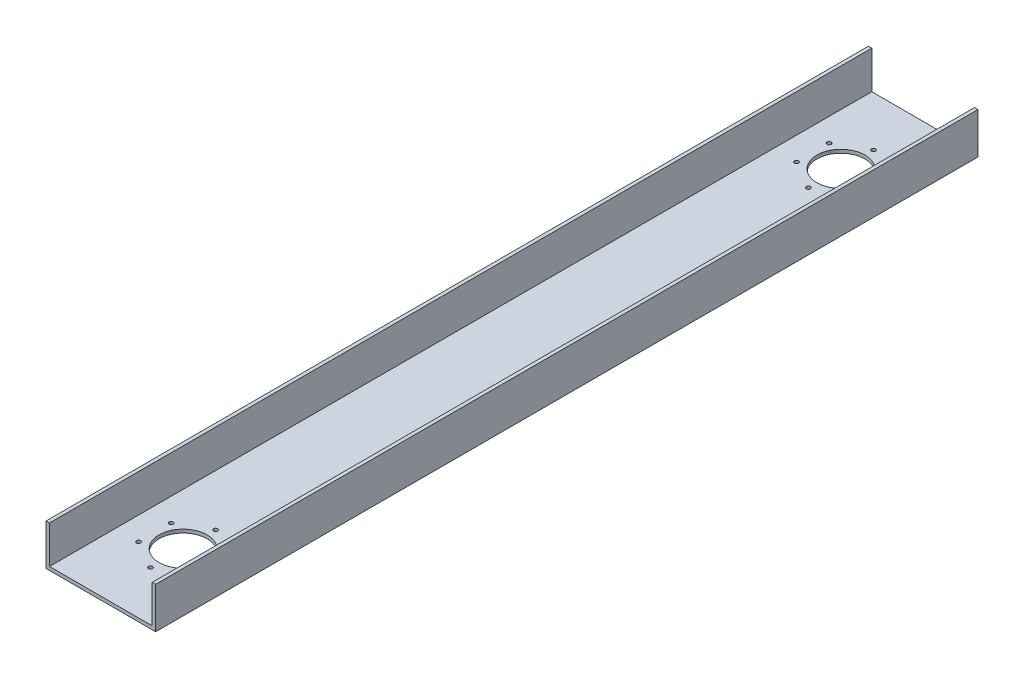
SolidWorks part; units mm, degrees
ref_plane "Front" through (0, 0, 0) normal (0, 0, 1) x (1, 0, 0)
ref_plane "Top" through (0, 0, 0) normal (0, 1, 0) x (1, 0, 0)
ref_plane "Right" through (0, 0, 0) normal (1, 0, 0) x (0, 0, -1)
sketch "Sketch1" plane through (0, 0, 0) normal (0, 0, 1) x (1, 0, 0)
  line L0 (3.175, 3.175) -> (3.175, 38.1)
  line L1 (0, 0) -> (101.6, 0)
  line L2 (0, 0) -> (0, 38.1)
  line L4 (101.6, 0) -> (101.6, 38.1)
  line L5 (3.175, 3.175) -> (98.425, 3.175)
  line L6 (98.425, 3.175) -> (98.425, 38.1)
  line L7 (0, 38.1) -> (3.175, 38.1)
  line L8 (101.6, 38.1) -> (98.425, 38.1)
  point P5 (0, 0)
  dimension "D1" = 38.1
  dimension "D2" = 101.6
  dimension "D3" = 3.175
extrude "Boss-Extrude1" add sketch "Sketch1" along normal blind 762
sketch "Sketch2" plane through (0, 0, 0) normal (0, -1, 0) x (1, 0, 0)
  line L0 (50.8, 762) -> (50.8, 685.8) construction
  line L1 (0, 762) -> (101.6, 762) construction
  circle A0 centre (50.8, 685.8) radius 22.2377
  dimension "D2" = 44.4754
  dimension "D1" = 76.2
extrude "Cut-Extrude1" cut sketch "Sketch2" against normal up to next
sketch "Sketch3" plane through (0, 0, 0) normal (0, -1, 0) x (1, 0, 0)
  line L0 (50.8, 685.8) -> (50.8, 715.9625) construction
  circle A0 centre (50.8, 715.9625) radius 1.8987
  circle A1 centre (76.9215, 700.8813) radius 1.8987
  circle A2 centre (76.9215, 670.7188) radius 1.8986
  circle A3 centre (50.8, 655.6375) radius 1.8987
  circle A4 centre (24.6785, 670.7187) radius 1.8987
  circle A5 centre (24.6785, 700.8812) radius 1.8987
  point P17 (50.8, 685.8)
  dimension "D2" = 3.7973
  dimension "D1" = 30.1625
  dimension "D3" = 6
extrude "Cut-Extrude2" cut sketch "Sketch3" against normal up to next
ref_plane "Mid_Plane" through (0, 0, 381) normal (0, 0, 1) x (1, 0, 0)
mirror "Mirror1" about plane through (0, 0, 381) normal (0, 0, 1) of "Cut-Extrude2", "Cut-Extrude1"
